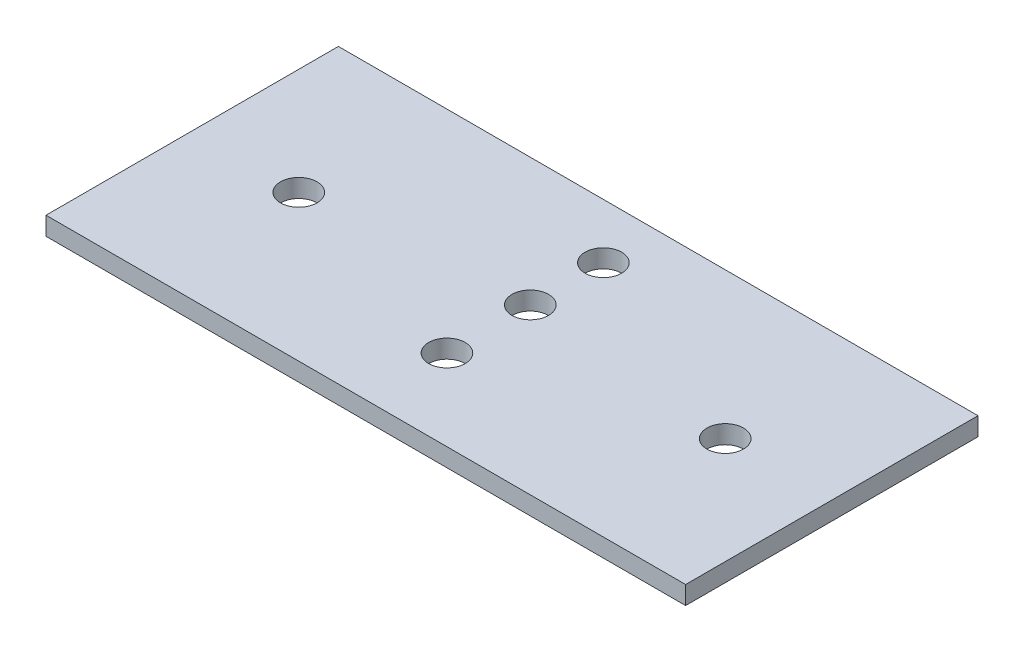
SolidWorks part; units mm, degrees
ref_plane "Front Plane" through (0, 0, 0) normal (0, 0, 1) x (1, 0, 0)
ref_plane "Top Plane" through (0, 0, 0) normal (0, 1, 0) x (1, 0, 0)
ref_plane "Right Plane" through (0, 0, 0) normal (1, 0, 0) x (0, 0, -1)
sketch "Sketch1" plane through (0, 0, 0) normal (1, 0, 0) x (0, 0, -1)
  line L0 (-16, 0) -> (16, 0)
  line L1 (-16, 0) -> (-16, 2)
  line L2 (-16, 2) -> (16, 2)
  line L3 (16, 2) -> (16, 0)
  point P2 (0, 0)
  dimension "D1" = 32
  dimension "D2" = 2
extrude "Boss-Extrude1" add sketch "Sketch1" along normal blind 35 and the other way blind 35
sketch "Sketch2" plane through (0, 2, 0) normal (0, 1, 0) x (1, 0, 0)
  line L0 (0, 16) -> (0, -16) construction
  line L1 (-35, 16) -> (35, 16) construction
  line L2 (-35, -16) -> (35, -16) construction
  line L3 (0, 0) -> (-23.335, 0) construction
  line L4 (0, 0) -> (23.335, 0) construction
  circle A0 centre (-23.335, 0) radius 2
  circle A1 centre (23.335, 0) radius 2
  dimension "D1" = 4
  dimension "D2" = 23.335
extrude "Cut-Extrude2" cut sketch "Sketch2" against normal up to surface (2 mm away) up to face at (0, 0, 0)
sketch "Sketch3" plane through (0, 2, 0) normal (0, 1, 0) x (1, 0, 0)
  line L0 (0, 16) -> (0, -16) construction
  line L1 (-35, 16) -> (35, 16) construction
  line L2 (-35, -16) -> (35, -16) construction
  line L3 (0, 10) -> (0, -7.12) construction
  circle A0 centre (0, 10) radius 2
  circle A1 centre (0, 2) radius 2
  circle A2 centre (0, -7.12) radius 2
  dimension "D1" = 4
  dimension "D2" = 8
  dimension "D3" = 6
  dimension "D4" = 17.12
extrude "Cut-Extrude3" cut sketch "Sketch3" against normal up to surface (2 mm away) up to face at (-23.335, 0, -2)
